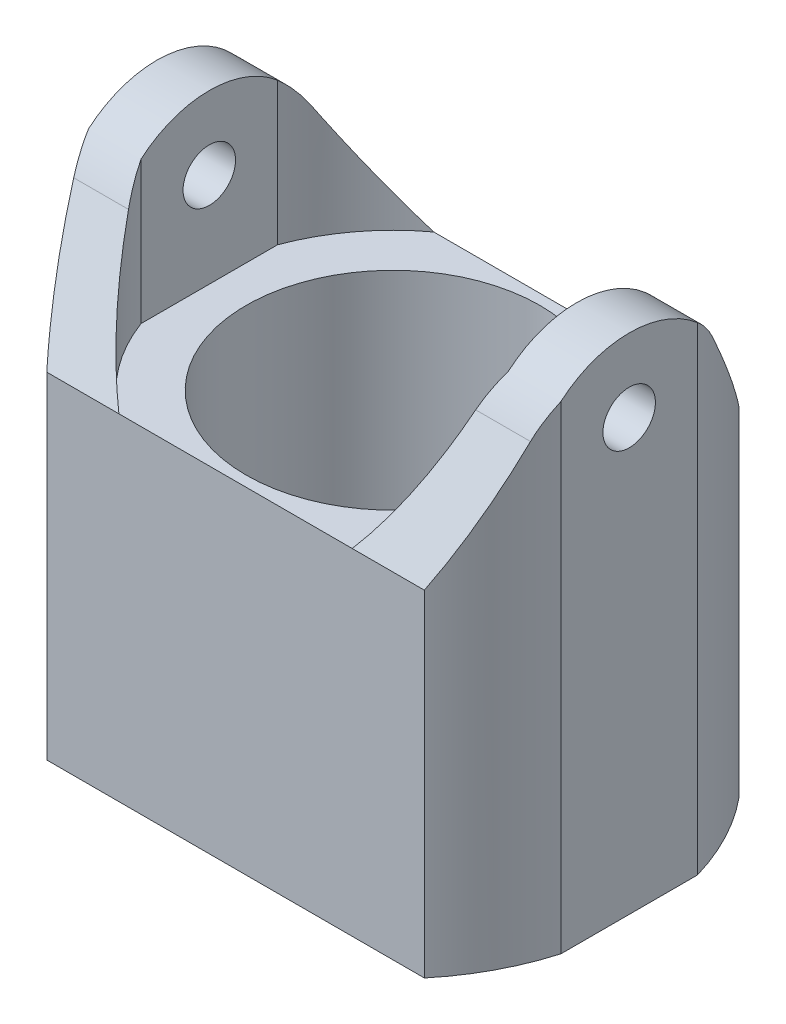
SolidWorks part; units mm, degrees
ref_plane "Front Plane" through (0, 0, 0) normal (0, 0, 1) x (1, 0, 0)
ref_plane "Top Plane" through (0, 0, 0) normal (0, 1, 0) x (1, 0, 0)
ref_plane "Right Plane" through (0, 0, 0) normal (1, 0, 0) x (0, 0, -1)
sketch "Sketch1" plane through (0, 0, 0) normal (0, 1, 0) x (1, 0, 0)
  line L0 (-22.5, -15) -> (22.5, -15)
  line L7 (-22.5, -15) -> (-22.5, 15)
  line L8 (-22.5, 15) -> (22.5, 15)
  line L9 (22.5, -15) -> (22.5, 15)
  line L10 (-22.5, -15) -> (22.5, 15) construction
  line L11 (-22.5, 15) -> (22.5, -15) construction
  circle A2 centre (0, 0) radius 14
  circle A7 centre (0, 0) radius 23.4201
  point P8 (0, 0)
  point P24 (22.5, 6.5)
  point P25 (22.5, -6.5)
  dimension "D1" = 28
  dimension "D4" = 30
  dimension "D5" = 45
  dimension "D9" = 13
extrude "Boss-Extrude1" add sketch "Sketch1" along normal blind 32 contours L0 A7 L9 L8 L7 A2 region at (-20.2067, 0, 10.7307)
ref_plane "Plane1" through (22.5, 0, 0) normal (1, 0, 0) x (0, 0, -1)
sketch "Sketch3" plane through (22.5, 0, 0) normal (1, 0, 0) x (0, 0, -1)
  line L0 (-15, 32) -> (15, 32)
  line L1 (15, 32) -> (15, 0) construction
  line L2 (15, 32) -> (0, 57.9808)
  line L3 (0, 57.9808) -> (-15, 32)
extrude "Boss-Extrude2" add sketch "Sketch3" against normal blind 45
sketch "Sketch4" plane through (0, 0, 0) normal (0, -1, 0) x (1, 0, 0)
  circle A0 centre (0, 0) radius 23.4201
  circle A1 centre (0, 0) radius 49.3971
  circle A2 centre (0, 0) radius 14
  circle M7 centre (0, 0) radius 14
  arc M9 (-17.9861, 15) -> (-22.5, 6.5) centre (0, 0) ccw
  arc M11 (-22.5, -6.5) -> (-17.9861, -15) centre (0, 0) ccw
  arc M13 (17.9861, -15) -> (22.5, -6.5) centre (0, 0) ccw
  arc M15 (22.5, 6.5) -> (17.9861, 15) centre (0, 0) ccw
extrude "Cut-Extrude1" cut sketch "Sketch4" against normal blind 90 contours M7 | A1 A0 M13 M11 M9 M15 region at (-47.9999, 0, 0) region at (0, 0, 0)
fillet "Fillet1" radius 10 2 edges at (-18.25, 57.9808, 0) (18.25, 57.9808, 0)
sketch "Sketch6" plane through (-22.5, 0, 0) normal (-1, 0, 0) x (0, 0, 1)
  circle A0 centre (0, 41) radius 2.5
  dimension "D1" = 5
  dimension "D2" = 41
extrude "Cut-Extrude2" cut sketch "Sketch6" against normal blind 90
ref_plane "Plane2" through (0, 50, 0) normal (0, 1, 0) x (1, 0, 0)
sketch "Sketch7" plane through (0, 50, 0) normal (0, 1, 0) x (1, 0, 0)
  line L0 (-17.9861, 15) -> (17.9861, 15) construction
  line L1 (-17.5, -15) -> (17.5, -15)
  line L2 (-17.5, -15) -> (-17.5, 15)
  line L3 (-17.5, 15) -> (17.5, 15)
  line L4 (17.5, -15) -> (17.5, 15)
  line L5 (-17.5, -15) -> (17.5, 15) construction
  line L6 (-17.5, 15) -> (17.5, -15) construction
  line L7 (-22.5, 6.5) -> (-22.5, -6.5) construction
  circle A2 centre (0, 0) radius 18.6682
  point P0 (0, 0)
  point P14 (17.5, 6.5)
  point P15 (17.5, -6.5)
  point P16 (0, 0)
  point P17 (0, 0)
  dimension "D1" = 13
  dimension "D2" = 5
extrude "Cut-Extrude3" cut sketch "Sketch7" against normal blind 18 contours L1 A2 L4 L3 L2 region at (0, 50, 0)
sketch "Sketch8" plane through (0, 0, 0) normal (0, -1, 0) x (1, 0, 0)
  line L0 (-15.5, -9) -> (15.5, -9) construction
  line L1 (-15.5, -9) -> (-15.5, 9) construction
  line L2 (-15.5, 9) -> (15.5, 9) construction
  line L3 (15.5, -9) -> (15.5, 9) construction
  line L4 (-15.5, -9) -> (15.5, 9) construction
  line L5 (-15.5, 9) -> (15.5, -9) construction
  circle A0 centre (-15.5, 9) radius 2.5
  circle A1 centre (15.5, 9) radius 2.5
  circle A2 centre (15.5, -9) radius 2.5
  circle A3 centre (-15.5, -9) radius 2.5
  point P8 (0, 0)
extrude "Cut-Extrude4" cut sketch "Sketch8" against normal blind 6
